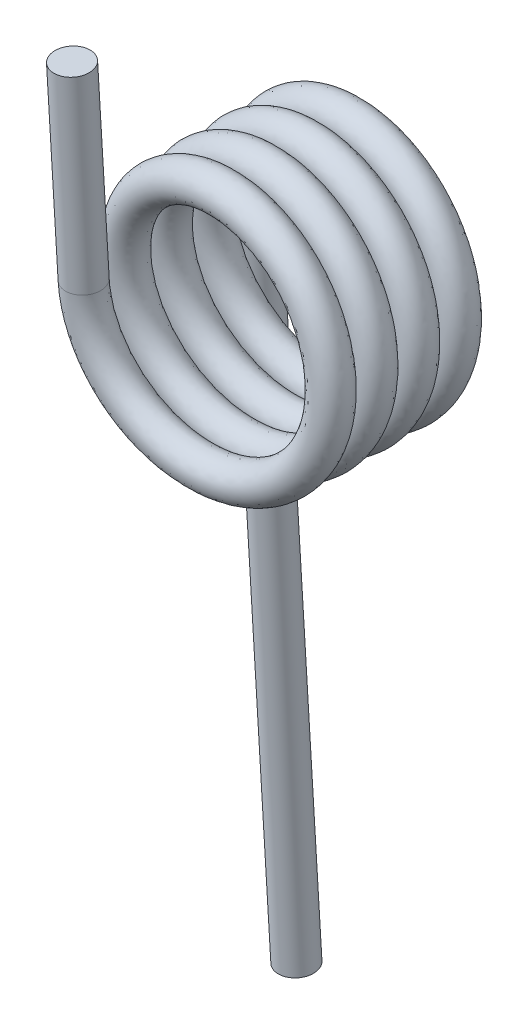
SolidWorks part; units mm, degrees
ref_plane "Front Plane" through (0, 0, 0) normal (0, 0, 1) x (1, 0, 0)
ref_plane "Top Plane" through (0, 0, 0) normal (0, 1, 0) x (1, 0, 0)
ref_plane "Right Plane" through (0, 0, 0) normal (1, 0, 0) x (0, 0, -1)
sketch "Sketch2" plane through (0, 0, 0) normal (0, 0, 1) x (1, 0, 0)
  circle A0 centre (0, 0) radius 40
  dimension "D1" = 80
curve "Helix/Spiral1" pitch 15 height 60 radius 40 left hand yes centre (0, 0, 0) axis (0, 0, 1) start towards (-1, 0, 0)
ref_plane "Plane1" through (-40, 0, 60) normal (0, 0.9982, 0.0596) x (-0.9707, 0.0143, -0.24)
sketch "Sketch3" plane through (-40, 0, 60) normal (0, 0.9982, 0.0596) x (-0.9707, 0.0143, -0.24)
  circle A0 centre (0.5428, 0.2726) radius 6.5
  dimension "D1" = 13
sweep "Sweep1" add profiles "Sketch3" path "Helix/Spiral1"
sketch "Sketch6" plane through (0, 3.5683, 0.213) normal (0, 0.9982, 0.0596) x (-0.9707, 0.0143, -0.24)
  circle A0 centre (24.97, 68.0261) radius 6.5
extrude "Boss-Extrude3" add sketch "Sketch6" along normal blind 70
sketch "Sketch7" plane through (0, 0, 0) normal (0, -0.9982, -0.0596) x (1, 0, 0)
  circle A0 centre (-39.4572, -0.2726) radius 6.5
extrude "Boss-Extrude4" add sketch "Sketch7" along normal blind 250
ref_axis "Axis1" through (0, 0, -29.4019) along (0, 0, 1)
